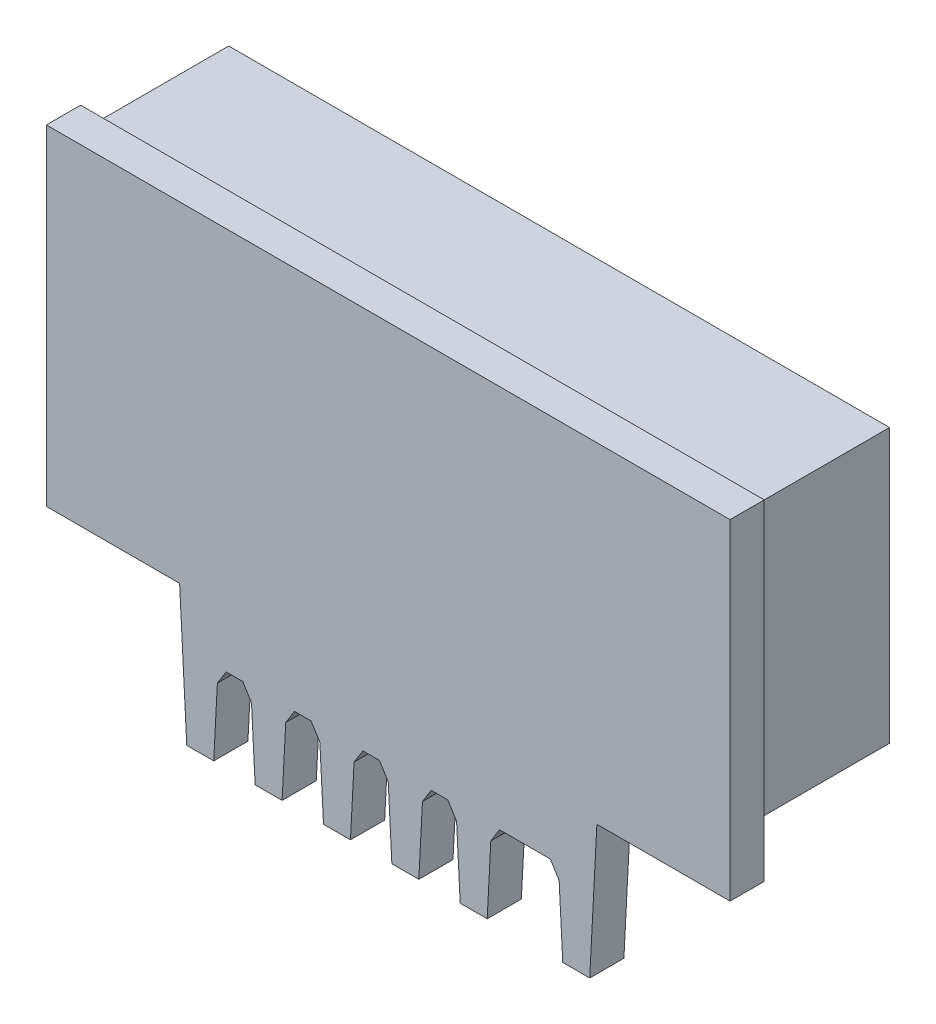
SolidWorks part; units mm, degrees
ref_plane "Front Plane" through (0, 0, 0) normal (0, 0, 1) x (1, 0, 0)
ref_plane "Top Plane" through (0, 0, 0) normal (0, 1, 0) x (1, 0, 0)
ref_plane "Right Plane" through (0, 0, 0) normal (1, 0, 0) x (0, 0, -1)
sketch "Sketch1" plane through (0, 0, 0) normal (0, 0, 1) x (1, 0, 0)
  line L0 (0, 0) -> (0, 20.5) construction
  line L1 (0, 20.5) -> (18.3124, 20.5) construction
  line L2 (18.3124, 20.5) -> (18.3124, 0) construction
  line L3 (18.3124, 0) -> (0, 0) construction
  line L4 (0, 3) -> (18.3124, 3) construction
  line L5 (0, 6) -> (18.3124, 6) construction
  line L6 (0.9062, 6) -> (0.9062, 0) construction
  line L7 (3.9062, 6) -> (3.9062, 0) construction
  line L8 (6.9062, 6) -> (6.9062, 0) construction
  line L9 (9.9062, 6) -> (9.9062, 0) construction
  line L10 (12.9062, 6) -> (12.9062, 0) construction
  line L11 (17.4062, 6) -> (17.4062, 0) construction
  line L12 (0.9062, 3) -> (3.9062, 3) construction
  line L13 (3.9062, 3) -> (6.9062, 3) construction
  line L14 (6.9062, 3) -> (9.9062, 3) construction
  line L15 (9.9062, 3) -> (12.9062, 3) construction
  line L16 (12.9062, 3) -> (17.4062, 3) construction
  line L17 (0.9062, 3) -> (0, 3) construction
  line L18 (17.4062, 3) -> (18.3124, 3) construction
  line L19 (2.4062, 3) -> (2.4062, 0) construction
  line L20 (5.4062, 3) -> (5.4062, 0) construction
  line L21 (8.4062, 3) -> (8.4062, 0) construction
  line L22 (11.4062, 3) -> (11.4062, 0) construction
  line L23 (15.1562, 3) -> (15.1562, 0) construction
  line L24 (14.4062, 3.75) -> (15.9062, 3.75) construction
  line L25 (0, 6) -> (0.3144, 0)
  line L26 (0.3144, 0) -> (1.4979, 0)
  line L27 (1.4979, 0) -> (1.6572, 3.0393)
  line L28 (3.1552, 3.0393) -> (3.3144, 0)
  line L29 (3.3144, 0) -> (4.4979, 0)
  line L30 (4.4979, 0) -> (4.6572, 3.0393)
  line L31 (6.1552, 3.0393) -> (6.3144, 0)
  line L32 (6.3144, 0) -> (7.4979, 0)
  line L33 (7.4979, 0) -> (7.6572, 3.0393)
  line L34 (9.1552, 3.0393) -> (9.3144, 0)
  line L35 (9.3144, 0) -> (10.4979, 0)
  line L36 (10.4979, 0) -> (10.6572, 3.0393)
  line L37 (12.1552, 3.0393) -> (12.3144, 0)
  line L38 (12.3144, 0) -> (13.4979, 0)
  line L39 (13.4979, 0) -> (13.6572, 3.0393)
  line L40 (16.6552, 3.0393) -> (16.8144, 0)
  line L41 (16.8144, 0) -> (17.9979, 0)
  line L42 (17.9979, 0) -> (18.3124, 6)
  line L44 (1.6572, 3.0393) -> (2.0426, 3.656)
  line L45 (0, 6) -> (-5.8438, 6)
  line L46 (-5.8438, 20.5) -> (24.1562, 20.5)
  line L47 (-5.8438, 6) -> (-5.8438, 20.5)
  line L48 (9.1562, 20.5) -> (9.1562, 6) construction
  line L49 (2.0426, 3.656) -> (2.7698, 3.656)
  line L50 (2.7698, 3.656) -> (3.1552, 3.0393)
  line L51 (4.6572, 3.0393) -> (5.0426, 3.656)
  line L52 (5.0426, 3.656) -> (5.7698, 3.656)
  line L53 (5.7698, 3.656) -> (6.1552, 3.0393)
  line L54 (7.6572, 3.0393) -> (8.0426, 3.656)
  line L55 (8.0426, 3.656) -> (8.7698, 3.656)
  line L56 (8.7698, 3.656) -> (9.1552, 3.0393)
  line L57 (10.6572, 3.0393) -> (11.0426, 3.656)
  line L58 (11.0426, 3.656) -> (11.7698, 3.656)
  line L59 (11.7698, 3.656) -> (12.1552, 3.0393)
  line L60 (13.6572, 3.0393) -> (14.0426, 3.656)
  line L61 (14.0426, 3.656) -> (16.2698, 3.656)
  line L62 (16.2698, 3.656) -> (16.6552, 3.0393)
  line L63 (18.3124, 6) -> (24.1562, 6)
  line L64 (24.1562, 6) -> (24.1562, 20.5)
  line L66 (23.6562, 20) -> (-5.3438, 20) construction
  line L67 (23.6562, 20) -> (23.6562, 8) construction
  line L68 (23.6562, 8) -> (-5.3438, 8) construction
  line L69 (-5.3438, 20) -> (-5.3438, 8) construction
  arc A0 (3.1552, 3.0393) -> (1.6572, 3.0393) centre (2.4062, 3) ccw construction
  arc A1 (6.1552, 3.0393) -> (4.6572, 3.0393) centre (5.4062, 3) ccw construction
  arc A2 (9.1552, 3.0393) -> (7.6572, 3.0393) centre (8.4062, 3) ccw construction
  arc A3 (12.1552, 3.0393) -> (10.6572, 3.0393) centre (11.4062, 3) ccw construction
  arc A4 (13.6572, 3.0393) -> (14.4062, 3.75) centre (14.4062, 3) cw construction
  arc A5 (16.6552, 3.0393) -> (15.9062, 3.75) centre (15.9062, 3) ccw construction
  dimension "D7" = 0.75
  dimension "D11" = 2
  dimension "D1" = 3
  dimension "D2" = 6
  dimension "D3" = 12
  dimension "D4" = 3
  dimension "D5" = 30
  dimension "D6" = 4.5
  dimension "D8" = 3
  dimension "D9" = 18.3124
  dimension "D10" = 20.5
  dimension "D12" = 14.5
  dimension "D13" = 0.5
  dimension "D14" = 0.5
  dimension "D15" = 29
extrude "Boss-Extrude1" add sketch "Sketch1" along normal blind 1.5
sketch "Sketch3" plane through (0, 0, 0) normal (0, 0, 1) x (1, 0, 0)
  line L0 (-0.4005, 6) -> (18.7129, 6)
  line L1 (18.7129, 3) -> (-0.4005, 3) construction
  line L2 (-0.4005, 0) -> (18.7129, 0) construction
  line L3 (-0.4005, -0.5) -> (18.7129, -0.5) construction
  line L4 (18.7129, -0.5) -> (18.7129, 6) construction
  line L5 (-0.4005, 6) -> (-0.4005, -0.5) construction
  line L6 (18.3124, 0) -> (0, 0) construction
  line L7 (0, 3) -> (18.3124, 3) construction
  line L8 (0, 6) -> (18.3124, 6) construction
  line L9 (0.3407, -0.5) -> (0, 6) construction
  line L10 (18.3124, 6) -> (17.9717, -0.5) construction
  line L11 (17.9979, 0) -> (18.3124, 6) construction
  line L12 (0, 6) -> (0.3144, 0) construction
  line L13 (5.4062, 6) -> (5.4062, -0.5) construction
  line L14 (3.9062, 6) -> (3.9062, -0.5) construction
  line L15 (5.4062, 3) -> (5.4062, 0) construction
  line L16 (3.1572, 3) -> (3.3407, -0.5) construction
  line L17 (2.7567, 3) -> (2.9401, -0.5)
  line L18 (3.1552, 3.0393) -> (3.3144, 0) construction
  line L19 (2.9401, -0.5) -> (4.8723, -0.5)
  line L20 (4.8723, -0.5) -> (5.0557, 3)
  line L21 (2.8484, 1.25) -> (3.2478, 1.2709) construction
  line L22 (5.9401, -0.5) -> (5.7567, 3)
  line L26 (7.8723, -0.5) -> (5.9401, -0.5)
  line L27 (8.0557, 3) -> (7.8723, -0.5)
  line L30 (2.4062, -0.5) -> (2.4062, 6) construction
  line L31 (2.4062, 3) -> (2.4062, 0) construction
  line L32 (8.4062, 6) -> (8.4062, -0.5) construction
  line L34 (11.4062, -0.5) -> (11.4062, 6) construction
  line L35 (15.1562, -0.5) -> (15.1562, 6) construction
  line L36 (8.4062, 3) -> (8.4062, 0) construction
  line L37 (11.4062, 3) -> (11.4062, 0) construction
  line L38 (15.1562, 3) -> (15.1562, 0) construction
  line L39 (10.8723, -0.5) -> (11.0557, 3)
  line L40 (8.9401, -0.5) -> (10.8723, -0.5)
  line L41 (8.7567, 3) -> (8.9401, -0.5)
  line L42 (11.9401, -0.5) -> (11.7567, 3)
  line L43 (13.8723, -0.5) -> (11.9401, -0.5)
  line L44 (14.0557, 3) -> (13.8723, -0.5)
  line L45 (16.4401, -0.5) -> (18.3723, -0.5)
  line L46 (16.2567, 3) -> (16.4401, -0.5)
  line L47 (18.3723, -0.5) -> (18.7129, 6)
  line L48 (1.8723, -0.5) -> (-0.0599, -0.5)
  line L49 (2.0557, 3) -> (1.8723, -0.5)
  line L50 (-0.0599, -0.5) -> (-0.4005, 6)
  line L51 (16.2567, 3) -> (14.0557, 3)
  line L52 (11.7567, 3) -> (11.0557, 3)
  line L53 (8.7567, 3) -> (8.0557, 3)
  line L54 (5.7567, 3) -> (5.0557, 3)
  line L55 (2.7567, 3) -> (2.0557, 3)
  dimension "D1" = 0.5
  dimension "D2" = 0.4
ref_plane "Plane1" through (3.9062, 0, 0) normal (1, 0, 0) x (0, 0, -1)
sketch "Sketch4" plane through (3.9062, 0, 0) normal (1, 0, 0) x (0, 0, -1)
  line L0 (0, 6) -> (0, -0.5) construction
  line L1 (0.6, 6) -> (-2.1, 6) construction
  line L2 (0.6, 6) -> (0.6, -0.5) construction
  line L3 (0.6, -0.5) -> (-2.1, -0.5) construction
  line L4 (-2.1, 6) -> (-2.1, -0.5) construction
  line L5 (-0.75, -0.5) -> (-0.75, 6) construction
  line L6 (-1.5, 6) -> (-1.5, -0.5) construction
  line L7 (0.6, 2.4005) -> (-2.1, 2.4005) construction
  line L8 (0.3, 6) -> (0.3, -0.5) construction
  line L9 (0.6, 2.4005) -> (3.846, 6) construction
  line L10 (2.2302, 6) -> (0.6, 4.1923) construction
  line L11 (0.6, 4.1923) -> (1.7139, 3.1878) construction
  line L12 (1.7139, 3.1878) -> (4.25, 6)
  line L13 (4.25, 6) -> (0.6, 6) construction
  line L14 (0.3, 1) -> (-1.8, 1) construction
  line L15 (-2.1, 0) -> (0.6, 0) construction
  line L16 (1.7139, 3.1878) -> (1.4912, 3.3887)
  line L17 (1.4912, 3.3887) -> (0.6, 2.4005)
  line L18 (-3.2139, 3.1878) -> (-5.75, 6)
  line L19 (-3.2139, 3.1878) -> (-2.9912, 3.3887)
  line L20 (-2.9912, 3.3887) -> (-2.1, 2.4005)
  line L21 (-2.1, 6) -> (-5.75, 6) construction
  line L22 (0.6, 3.0724) -> (3.2401, 6) construction
  arc A0 (0.4965, 2.2224) -> (0.6, -0.5) centre (4.2, 1) ccw
  arc A1 (0.6, 2.4005) -> (0.4965, 2.2224) centre (0.9713, 2.0656) ccw
  arc A2 (-2.1, 2.4005) -> (-1.9965, 2.2224) centre (-2.4713, 2.0656) cw
  arc A3 (-1.9965, 2.2224) -> (-2.1, -0.5) centre (-5.7, 1) cw
  dimension "D6" = 0.5
  dimension "D1" = 0.6
  dimension "D2" = 0.3
  dimension "D3" = 1.5
  dimension "D4" = 1
  dimension "D5" = 0.3
  dimension "D7" = 10
sketch "Sketch5" plane through (0, 0, 0) normal (1, 0, 0) x (0, 0, -1)
  line L0 (2.2302, 6) -> (0.6, 4.1923) construction
  line L1 (0.6, 4.1923) -> (1.7139, 3.1878) construction
  line L2 (1.7139, 3.1878) -> (4.25, 6) construction
  line L3 (2.2302, 6) -> (0.6, 4.1923) construction
  line L4 (0.6, 4.1923) -> (1.7139, 3.1878) construction
  line L5 (1.7139, 3.1878) -> (4.25, 6) construction
ref_plane "Plane2" through (0, 2.6105, -2.3541) normal (0, 0.7426, -0.6697) x (1, 0, 0)
sketch "Sketch6" plane through (0, 2.6105, -2.3541) normal (0, 0.7426, -0.6697) x (1, 0, 0)
  line L1 (3.9062, -2.362) -> (3.9062, -0.862) construction
  line L2 (3.9062, -2.362) -> (3.9062, -5.0612) construction
  line L3 (4.6562, -5.0612) -> (3.1562, -5.0612)
  line L4 (4.6562, -1.612) -> (3.1562, -1.612) construction
  line L5 (3.1562, -1.612) -> (3.1562, -5.0612)
  line L6 (4.6562, -1.612) -> (4.6562, -5.0612)
  line L10 (2.4062, -5.0612) -> (15.1562, -5.0612) construction
  line L11 (15.1562, -5.0612) -> (15.1562, -0.862) construction
  line L12 (15.1562, -0.862) -> (2.4062, -0.862) construction
  line L13 (2.4062, -0.862) -> (2.4062, -5.0612) construction
  line L14 (15.1562, 0.3349) -> (15.1562, -4.0182) construction
  line L15 (2.4062, 0.3349) -> (2.4062, -4.0182) construction
  line L16 (11.4062, -5.0612) -> (11.4062, -0.862) construction
  line L17 (8.4062, -5.0612) -> (8.4062, -0.862) construction
  line L18 (5.4062, -5.0612) -> (5.4062, -0.862) construction
  line L19 (5.4062, -4.0182) -> (5.4062, 0.3349) construction
  line L20 (8.4062, -4.0182) -> (8.4062, 0.3349) construction
  line L21 (11.4062, 0.3349) -> (11.4062, -4.0182) construction
  line L22 (0.1562, -1.612) -> (0.1562, -5.0612)
  line L23 (0.1562, -5.0612) -> (1.6562, -5.0612)
  line L24 (1.6562, -1.612) -> (1.6562, -5.0612)
  line L25 (7.6562, -1.612) -> (7.6562, -5.0612)
  line L26 (6.1562, -5.0612) -> (7.6562, -5.0612)
  line L27 (6.1562, -1.612) -> (6.1562, -5.0612)
  line L28 (10.6562, -1.612) -> (10.6562, -5.0612)
  line L29 (10.6562, -5.0612) -> (9.1562, -5.0612)
  line L30 (9.1562, -1.612) -> (9.1562, -5.0612)
  line L31 (13.6562, -1.612) -> (13.6562, -5.0612)
  line L32 (12.1562, -5.0612) -> (13.6562, -5.0612)
  line L33 (12.1562, -1.612) -> (12.1562, -5.0612)
  line L34 (18.1562, -1.612) -> (18.1562, -5.0612)
  line L35 (18.1562, -5.0612) -> (16.6562, -5.0612)
  line L36 (16.6562, -1.612) -> (16.6562, -5.0612)
  circle A0 centre (3.9062, -1.612) radius 0.75 construction
  arc A1 (4.6562, -1.612) -> (3.1562, -1.612) centre (3.9062, -1.612) ccw
  arc A2 (0.1562, -1.612) -> (1.6562, -1.612) centre (0.9062, -1.612) cw
  arc A3 (6.1562, -1.612) -> (7.6562, -1.612) centre (6.9062, -1.612) cw
  arc A4 (10.6562, -1.612) -> (9.1562, -1.612) centre (9.9062, -1.612) ccw
  arc A5 (12.1562, -1.612) -> (13.6562, -1.612) centre (12.9062, -1.612) cw
  arc A6 (18.1562, -1.612) -> (16.6562, -1.612) centre (17.4062, -1.612) ccw
ref_plane "Plane3" through (0, 1.6223, -1.463) normal (0, 0.7426, -0.6697) x (1, 0, 0)
sketch "Sketch7" plane through (0, 1.6223, -1.463) normal (0, 0.7426, -0.6697) x (1, 0, 0)
  line L0 (3.1562, -1.612) -> (3.1562, -5.0612) construction
  line L1 (4.6562, -5.0612) -> (3.1562, -5.0612) construction
  line L2 (4.6562, -1.612) -> (4.6562, -5.0612) construction
  line L3 (3.1562, -1.612) -> (3.1562, -5.0612) construction
  line L4 (4.6562, -5.0612) -> (3.1562, -5.0612) construction
  line L5 (4.6562, -1.612) -> (4.6562, -5.0612) construction
  line L6 (3.9062, -0.862) -> (3.9062, -5.0612) construction
  line L7 (4.6562, -1.612) -> (3.1562, -1.612) construction
  line L8 (4.6562, -2.362) -> (3.1562, -2.362) construction
  line L9 (3.4562, -1.612) -> (3.4562, -2.362)
  line L10 (3.4562, -2.362) -> (4.3562, -2.362)
  line L11 (4.3562, -2.362) -> (4.3562, -1.612)
  line L12 (2.4062, -0.862) -> (2.4062, -5.0612) construction
  line L13 (2.4062, -5.0612) -> (15.1562, -5.0612) construction
  line L14 (15.1562, -0.862) -> (2.4062, -0.862) construction
  line L15 (5.4062, -5.0612) -> (5.4062, -0.862) construction
  line L16 (8.4062, -5.0612) -> (8.4062, -0.862) construction
  line L17 (11.4062, -5.0612) -> (11.4062, -0.862) construction
  line L18 (15.1562, -5.0612) -> (15.1562, -0.862) construction
  line L19 (2.4062, -0.862) -> (2.4062, -5.0612) construction
  line L20 (2.4062, -5.0612) -> (15.1562, -5.0612) construction
  line L21 (15.1562, -0.862) -> (2.4062, -0.862) construction
  line L22 (5.4062, -5.0612) -> (5.4062, -0.862) construction
  line L23 (8.4062, -5.0612) -> (8.4062, -0.862) construction
  line L24 (11.4062, -5.0612) -> (11.4062, -0.862) construction
  line L25 (15.1562, -5.0612) -> (15.1562, -0.862) construction
  line L26 (0.4562, -2.362) -> (0.4562, -1.612)
  line L27 (1.3562, -2.362) -> (0.4562, -2.362)
  line L28 (1.3562, -1.612) -> (1.3562, -2.362)
  line L29 (7.3562, -2.362) -> (6.4562, -2.362)
  line L30 (7.3562, -1.612) -> (7.3562, -2.362)
  line L31 (6.4562, -2.362) -> (6.4562, -1.612)
  line L32 (9.4562, -1.612) -> (9.4562, -2.362)
  line L33 (10.3562, -2.362) -> (10.3562, -1.612)
  line L34 (9.4562, -2.362) -> (10.3562, -2.362)
  line L35 (13.3562, -1.612) -> (13.3562, -2.362)
  line L36 (12.4562, -2.362) -> (12.4562, -1.612)
  line L37 (13.3562, -2.362) -> (12.4562, -2.362)
  line L38 (16.9562, -1.612) -> (16.9562, -2.362)
  line L39 (17.8562, -2.362) -> (17.8562, -1.612)
  line L40 (16.9562, -2.362) -> (17.8562, -2.362)
  arc A0 (4.6562, -1.612) -> (3.1562, -1.612) centre (3.9062, -1.612) ccw construction
  arc A1 (4.6562, -1.612) -> (3.1562, -1.612) centre (3.9062, -1.612) ccw construction
  circle A2 centre (3.9062, -1.612) radius 0.45 construction
  arc A3 (4.3562, -1.612) -> (3.4562, -1.612) centre (3.9062, -1.612) ccw
  arc A4 (0.4562, -1.612) -> (1.3562, -1.612) centre (0.9062, -1.612) cw
  arc A5 (6.4562, -1.612) -> (7.3562, -1.612) centre (6.9062, -1.612) cw
  arc A6 (10.3562, -1.612) -> (9.4562, -1.612) centre (9.9062, -1.612) ccw
  arc A7 (12.4562, -1.612) -> (13.3562, -1.612) centre (12.9062, -1.612) cw
  arc A8 (17.8562, -1.612) -> (16.9562, -1.612) centre (17.4062, -1.612) ccw
ref_plane "bisect" through (0, 0, 0.75) normal (0, 0, 1) x (1, 0, 0)
ref_plane "insert_surface" through (0, 6, 0) normal (0, 1, 0) x (1, 0, 0)
sketch "Sketch8" plane through (0, 6, 0) normal (0, 1, 0) x (1, 0, 0)
  line L0 (18.7129, -0.75) -> (-0.4005, -0.75) construction
  line L1 (-0.4005, 0.6) -> (18.7129, 0.6)
  line L2 (-0.4005, 0.6) -> (-0.4005, -2.1)
  line L3 (-0.4005, -2.1) -> (18.7129, -2.1)
  line L4 (18.7129, 0.6) -> (18.7129, -2.1)
  line L5 (9.1562, 0.6) -> (9.1562, -2.1) construction
  line L6 (0, 0) -> (18.3124, 0) construction
  line L7 (0, 0) -> (0, -1.5) construction
  line L8 (0, -1.5) -> (18.3124, -1.5) construction
  line L9 (18.3124, 0) -> (18.3124, -1.5) construction
  line L10 (18.7129, 0.3) -> (-0.4005, 0.3) construction
  line L11 (18.7129, -1.8) -> (-0.4005, -1.8) construction
sketch "Sketch9" plane through (0, 0, 0) normal (0, 0, 1) x (1, 0, 0)
  line L0 (18.3723, -0.5) -> (18.7129, 6) construction
  line L1 (-0.4005, 6) -> (18.7129, 6) construction
  line L2 (-0.0599, -0.5) -> (-0.4005, 6) construction
  line L3 (1.8723, -0.5) -> (-0.0599, -0.5) construction
  line L4 (2.0557, 3) -> (1.8723, -0.5) construction
  line L5 (2.7567, 3) -> (2.0557, 3) construction
  line L6 (2.7567, 3) -> (2.9401, -0.5) construction
  line L7 (2.9401, -0.5) -> (4.8723, -0.5) construction
  line L8 (4.8723, -0.5) -> (5.0557, 3) construction
  line L9 (5.7567, 3) -> (5.0557, 3) construction
  line L10 (5.9401, -0.5) -> (5.7567, 3) construction
  line L11 (7.8723, -0.5) -> (5.9401, -0.5) construction
  line L12 (8.0557, 3) -> (7.8723, -0.5) construction
  line L13 (8.7567, 3) -> (8.0557, 3) construction
  line L14 (8.7567, 3) -> (8.9401, -0.5) construction
  line L15 (8.9401, -0.5) -> (10.8723, -0.5) construction
  line L16 (10.8723, -0.5) -> (11.0557, 3) construction
  line L17 (11.7567, 3) -> (11.0557, 3) construction
  line L18 (11.9401, -0.5) -> (11.7567, 3) construction
  line L19 (13.8723, -0.5) -> (11.9401, -0.5) construction
  line L20 (14.0557, 3) -> (13.8723, -0.5) construction
  line L21 (16.2567, 3) -> (14.0557, 3) construction
  line L22 (16.2567, 3) -> (16.4401, -0.5) construction
  line L23 (16.4401, -0.5) -> (18.3723, -0.5) construction
  line L24 (18.3723, -0.5) -> (18.7129, 6)
  line L25 (-0.4005, 6) -> (18.7129, 6) construction
  line L26 (-0.0599, -0.5) -> (-0.4005, 6)
  line L27 (1.8723, -0.5) -> (-0.0599, -0.5)
  line L28 (2.0557, 3) -> (1.8723, -0.5)
  line L29 (2.7567, 3) -> (2.0557, 3) construction
  line L30 (2.7567, 3) -> (2.9401, -0.5)
  line L31 (2.9401, -0.5) -> (4.8723, -0.5)
  line L32 (4.8723, -0.5) -> (5.0557, 3)
  line L33 (5.7567, 3) -> (5.0557, 3) construction
  line L34 (5.9401, -0.5) -> (5.7567, 3)
  line L35 (7.8723, -0.5) -> (5.9401, -0.5)
  line L36 (8.0557, 3) -> (7.8723, -0.5)
  line L37 (8.7567, 3) -> (8.0557, 3) construction
  line L38 (8.7567, 3) -> (8.9401, -0.5)
  line L39 (8.9401, -0.5) -> (10.8723, -0.5)
  line L40 (10.8723, -0.5) -> (11.0557, 3)
  line L41 (11.7567, 3) -> (11.0557, 3) construction
  line L42 (11.9401, -0.5) -> (11.7567, 3)
  line L43 (13.8723, -0.5) -> (11.9401, -0.5)
  line L44 (14.0557, 3) -> (13.8723, -0.5)
  line L45 (16.2567, 3) -> (14.0557, 3) construction
  line L46 (16.2567, 3) -> (16.4401, -0.5)
  line L47 (16.4401, -0.5) -> (18.3723, -0.5)
  line L48 (16.2567, 3) -> (16.2567, 6)
  line L49 (14.0557, 3) -> (14.0557, 6)
  line L50 (11.7567, 3) -> (11.7567, 6)
  line L51 (18.7129, 6) -> (-0.4005, 6) construction
  line L52 (11.0557, 3) -> (11.0557, 6)
  line L53 (-0.4005, 6) -> (18.7129, 6) construction
  line L54 (8.7567, 3) -> (8.7567, 6)
  line L55 (8.0557, 3) -> (8.0557, 6)
  line L58 (5.7567, 3) -> (5.7567, 6)
  line L60 (5.0557, 3) -> (5.0557, 6)
  line L62 (15.1562, -0.5) -> (15.1562, 6) construction
  line L63 (15.1562, -0.5) -> (15.1562, 6) construction
  line L64 (2.7567, 3) -> (2.7567, 6)
  line L65 (2.0557, 3) -> (2.0557, 6)
  line L67 (18.7129, 6) -> (16.2567, 6)
  line L68 (14.0557, 6) -> (11.7567, 6)
  line L69 (11.0557, 6) -> (8.7567, 6)
  line L70 (8.0557, 6) -> (5.7567, 6)
  line L71 (5.0557, 6) -> (2.7567, 6)
  line L72 (2.0557, 6) -> (-0.4005, 6)
sketch "Sketch11" plane through (0, 6, 0) normal (0, 1, 0) x (1, 0, 0)
  line L0 (9.1562, -0.75) -> (9.1562, -5.75) construction
  line L1 (-0.8438, 4.25) -> (19.1562, 4.25)
  line L2 (-0.8438, 4.25) -> (-0.8438, -5.75)
  line L3 (-0.8438, -5.75) -> (19.1562, -5.75)
  line L4 (19.1562, 4.25) -> (19.1562, -5.75)
  line L5 (9.1562, -0.75) -> (9.1562, 4.25) construction
  line L6 (9.1562, -0.75) -> (19.1562, -0.75) construction
  line L7 (9.1562, -0.75) -> (-0.8438, -0.75) construction
  line L8 (-10.5124, -0.75) -> (10.5124, -0.75) construction
  dimension "D1" = 10
  dimension "D2" = 20
sketch "Sketch12" plane through (0, 0, 0) normal (0, 0, 1) x (1, 0, 0)
  line L0 (-5.3438, 20) -> (-5.3438, 8)
  line L1 (-5.3438, 8) -> (23.6562, 8)
  line L2 (23.6562, 8) -> (23.6562, 20)
  line L3 (23.6562, 20) -> (-5.3438, 20)
  line L4 (23.6562, 8) -> (-5.3438, 8) construction
  line L8 (23.6562, 20) -> (-5.3438, 20) construction
  line L9 (-5.3438, 20) -> (-5.3438, 8) construction
  line L10 (23.6562, 20) -> (23.6562, 8) construction
extrude "Boss-Extrude2" add sketch "Sketch12" against normal blind 6
